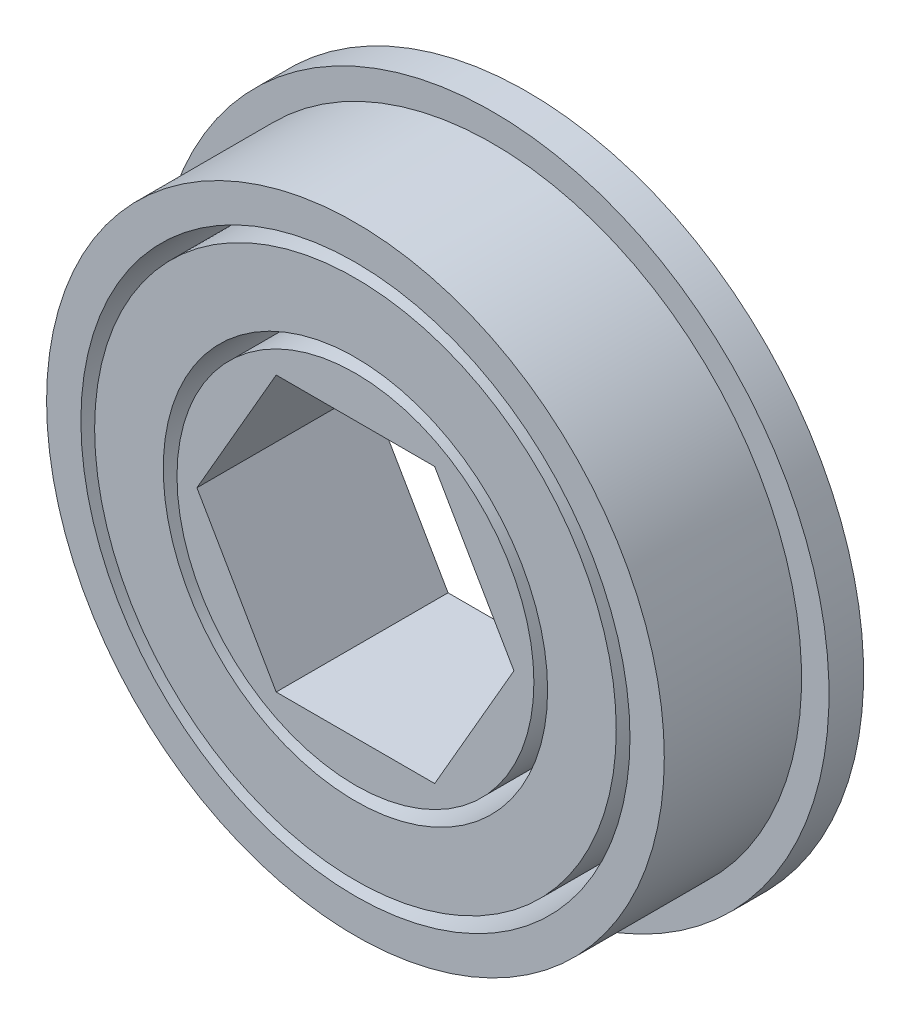
SolidWorks part; units mm, degrees
material "AISI 304"
ref_plane "Alzado" through (0, 0, 0) normal (0, 0, 1) x (1, 0, 0)
ref_plane "Planta" through (0, 0, 0) normal (0, 1, 0) x (1, 0, 0)
ref_plane "Vista lateral" through (0, 0, 0) normal (1, 0, 0) x (0, 0, -1)
sketch "Croquis1" plane through (0, 0, 0) normal (0, 0, 1) x (1, 0, 0)
  line L1 (7.3323, 0) -> (3.6662, 6.35)
  line L2 (3.6662, 6.35) -> (-3.6662, 6.35)
  line L3 (-3.6662, 6.35) -> (-7.3323, 0)
  line L4 (-7.3323, 0) -> (-3.6662, -6.35)
  line L5 (-3.6662, -6.35) -> (3.6662, -6.35)
  line L6 (3.6662, -6.35) -> (7.3323, 0)
  circle A0 centre (0, 0) radius 6.35 construction
  circle A1 centre (0, 0) radius 14.2875
  dimension "D2" = 28.575
  dimension "D1" = 12.7
extrude "Saliente-Extruir1" add sketch "Croquis1" along normal blind 7.9502
sketch "Croquis2" plane through (0, 0, 0) normal (0, 0, -1) x (-1, 0, 0)
  circle A0 centre (0, 0) radius 15.5575
  circle A1 centre (0, 0) radius 14.2875
  dimension "D1" = 31.115
  dimension "D2" = 28.575
extrude "Saliente-Extruir2" add sketch "Croquis2" against normal blind 1.6002
sketch "Croquis3" plane through (0, 0, 7.9502) normal (0, 0, 1) x (1, 0, 0)
  circle A0 centre (0, 0) radius 8.255
  circle A1 centre (0, 0) radius 8.89
  circle A2 centre (0, 0) radius 12.7
  circle A3 centre (0, 0) radius 12.065
  dimension "D1" = 25.4
  dimension "D2" = 24.13
  dimension "D3" = 17.78
  dimension "D4" = 16.51
extrude "Cortar-Extruir1" cut sketch "Croquis3" against normal blind 25.4 contours A2 A3 | A1 A0 region at (-8.6386, 0, 7.9502) region at (-12.3408, 0, 7.9502)
